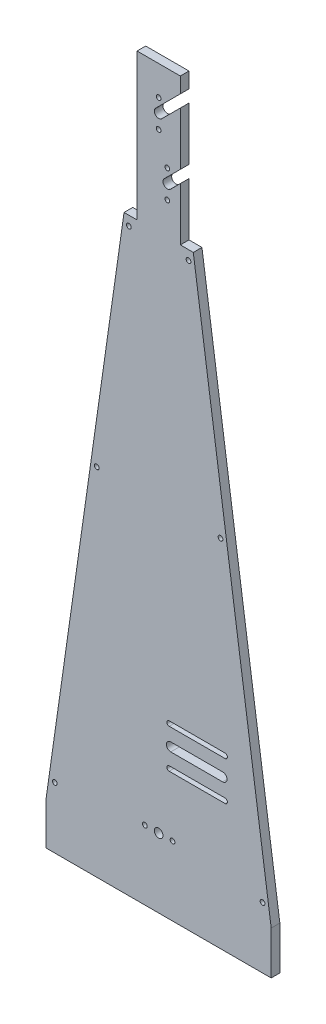
SolidWorks part; units mm, degrees
ref_plane "Ebene vorne" through (0, 0, 0) normal (0, 0, 1) x (1, 0, 0)
ref_plane "Ebene oben" through (0, 0, 0) normal (0, 1, 0) x (1, 0, 0)
ref_plane "Ebene rechts" through (0, 0, 0) normal (1, 0, 0) x (0, 0, -1)
sketch "Skizze1" plane through (0, 0, 0) normal (0, 0, 1) x (1, 0, 0)
  line L0 (-40, 681) -> (-130, 50)
  line L1 (-263.5092, 681) -> (296.6943, 681) construction
  line L2 (0, 800) -> (0, 0)
  line L3 (-25, 800) -> (-25, 681)
  line L4 (-40, 681) -> (-25, 681)
  line L5 (0, 800) -> (0, 850)
  line L7 (-130, 0) -> (-130, 50)
  line L10 (40, 681) -> (25, 681)
  line L12 (-130, 0) -> (0, 0)
  line L13 (-32.9292, 681) -> (-123.0701, 49.0116) construction
  line L14 (-33.0701, 680.0116) -> (-123.0701, 49.0116) construction
  line L15 (-25, 800) -> (-25, 850)
  line L16 (-25, 850) -> (0, 850)
  point P2 (0, 800)
  point P4 (0, 681)
  point P8 (-40, 681)
  point P12 (-119.9898, 70.6083)
  point P18 (-71.4708, 410.7801)
  point P21 (-34.4874, 670.075)
  point P23 (0, 816)
  point P24 (0, 784)
  dimension "D2" = 25
  dimension "D5" = 50
  dimension "D6" = 130
  dimension "D1" = 800
  dimension "D3" = 119
  dimension "D4" = 40
  dimension "D8" = 50
  dimension "D9" = 16
  dimension "D10" = 16
  dimension "D7" = 7
extrude "Aufsatz-Linear austragen1" add sketch "Skizze1" along normal blind 10 contours L2 L12 L7 L0 L4 L3 L15 L16 L5
mirror "Spiegeln1" about plane through (0, 800, 10) normal (1, 0, 0) of "Aufsatz-Linear austragen1"
sketch "Skizze17" plane through (0, 0, 10) normal (0, 0, 1) x (1, 0, 0)
  line L0 (0, 800) -> (28.5355, 828.5355) construction
  line L1 (-3.5355, 803.5355) -> (25, 832.0711)
  line L2 (3.5355, 796.4645) -> (32.0711, 825)
  line L3 (-25, 850) -> (25, 850) construction
  line L4 (25, 850) -> (25, 681) construction
  line L5 (10, 734.4448) -> (28.5355, 752.9803) construction
  line L6 (6.4645, 737.9803) -> (25, 756.5159)
  line L7 (13.5355, 730.9093) -> (32.0711, 749.4448)
  line L8 (-25, 850) -> (0, 850) construction
  line L9 (10, 850) -> (10, 681) construction
  line L10 (-263.5092, 681) -> (296.6943, 681) construction
  arc A0 (-3.5355, 803.5355) -> (3.5355, 796.4645) centre (0, 800) ccw
  arc A1 (32.0711, 825) -> (25, 832.0711) centre (28.5355, 828.5355) ccw
  circle A2 centre (0, 816) radius 2.75
  circle A3 centre (0, 784) radius 2.75
  arc A4 (6.4645, 737.9803) -> (13.5355, 730.9093) centre (10, 734.4448) ccw
  arc A5 (32.0711, 749.4448) -> (25, 756.5159) centre (28.5355, 752.9803) ccw
  circle A6 centre (10, 750.4448) radius 2.75
  circle A7 centre (10, 718.4448) radius 2.75
  point P2 (14.2678, 814.2678)
  point P20 (19.2678, 743.7126)
  point P35 (10, 734.4448)
  dimension "D2" = 5
  dimension "D3" = 5.5
  dimension "D4" = 5.5
  dimension "D6" = 5
  dimension "D10" = 5.5
  dimension "D11" = 5.5
  dimension "D1" = 45
  dimension "D5" = 45
  dimension "D7" = 15
  dimension "D8" = 16
  dimension "D9" = 16
extrude "Schnitt-Linear austragen1" cut sketch "Skizze17" against normal blind 10
hole_wizard "Ø10.0 (10) Durchmesser Bohrung1" positions "Skizze6" profile "Skizze5" hole size "Ø10.0" standard "ISO" end condition through all
sketch "Skizze6" plane through (0, 0, 10) normal (0, 0, 1) x (1, 0, 0)
  line L0 (0, 800) -> (0, 0) construction
  line L1 (-130, 0) -> (130, 0) construction
  point P3 (0, 80)
  point P18 (0, 0)
  dimension "D1" = 80
sketch "Skizze5" plane through (0, 80, 10) normal (1, 0, 0) x (0, -1, 0)
  line L0 (0, 0) -> (0, 10)
  line L1 (0, 10) -> (5, 10)
  line L2 (5, 10) -> (5, 0)
  line L5 (5, 0) -> (0, 0)
  line L11 (0, -6.35) -> (0, 107.95) construction
  dimension "Bohrerdurchmesser" = 10
  dimension "Bohrungstiefe" = 10
hole_wizard "Ø5.5 (5.5) Durchmesser Bohrung2" positions "Skizze7" profile "Skizze8" hole size "Ø5.5" standard "ISO" end condition through all
sketch "Skizze7" plane through (0, 0, 10) normal (0, 0, 1) x (1, 0, 0)
  line L1 (0, 80) -> (-104.9668, 80) construction
  line L3 (0, 80) -> (96.42, 80) construction
  circle A0 centre (0, 80) radius 5 construction
  point P0 (-16, 80)
  point P4 (16, 80)
  dimension "D1" = 16
  dimension "D2" = 16
sketch "Skizze8" plane through (-16, 80, 10) normal (1, 0, 0) x (0, -1, 0)
  line L0 (0, 0) -> (0, 10)
  line L1 (0, 10) -> (2.75, 10)
  line L2 (2.75, 10) -> (2.75, 0)
  line L5 (2.75, 0) -> (0, 0)
  line L11 (0, -6.35) -> (0, 107.95) construction
  dimension "Bohrerdurchmesser" = 5.5
  dimension "Bohrungstiefe" = 10
hole_wizard "Ø10.0 (10) Durchmesser Langloch1" positions "Skizze9" profile "Skizze10" size "Ø10.0" standard "ISO" slot yes end condition through all
sketch "Skizze9" plane through (0, 0, 10) normal (0, 0, 1) x (1, 0, 0)
  line L0 (8.9197, 173.191) -> (78.9197, 173.191) construction
  point P0 (43.9197, 173.191)
  dimension "D1" = 70
sketch "Skizze10" plane through (43.9197, 173.191, 10) normal (1, 0, 0) x (0, -1, 0)
  line L0 (0, 0) -> (0, 10)
  line L1 (0, 10) -> (5, 10)
  line L2 (5, 10) -> (5, 0)
  line L5 (5, 0) -> (0, 0)
  line L11 (0, -6.35) -> (0, 107.95) construction
  dimension "Bohrerdurchmesser" = 10
  dimension "Bohrungstiefe" = 10
hole_wizard "Ø5.5 (5.5) Durchmesser Langloch1" positions "Skizze13" profile "Skizze14" size "Ø5.5" standard "ISO" slot yes end condition through all
sketch "Skizze13" plane through (0, 0, 10) normal (0, 0, 1) x (1, 0, 0)
  line L0 (9.3832, 195.691) -> (79.3832, 195.691) construction
  line L1 (44.3832, 195.691) -> (44.3832, 150.691) construction
  arc A0 (13.9197, 178.191) -> (13.9197, 168.191) centre (13.9197, 173.191) ccw construction
  point P0 (44.3832, 195.691)
  point P4 (44.3832, 150.691)
  point P10 (8.9197, 173.191)
  dimension "D1" = 70
  dimension "D2" = 22.5
  dimension "D3" = 22.5
sketch "Skizze14" plane through (44.3832, 195.691, 10) normal (1, 0, 0) x (0, -1, 0)
  line L0 (0, 0) -> (0, 10)
  line L1 (0, 10) -> (2.75, 10)
  line L2 (2.75, 10) -> (2.75, 0)
  line L5 (2.75, 0) -> (0, 0)
  line L11 (0, -6.35) -> (0, 107.95) construction
  dimension "Bohrerdurchmesser" = 5.5
  dimension "Bohrungstiefe" = 10
hole_wizard "Ø5.5 (5.5) Durchmesser Bohrung3" positions "Skizze19" profile "Skizze18" hole size "Ø5.5" standard "ISO" end condition through all
sketch "Skizze19" plane through (0, 0, 10) normal (0, 0, 1) x (1, 0, 0)
  point P0 (-34.4874, 670.075)
  point P3 (-71.4708, 410.7801)
  point P6 (-119.9898, 70.6083)
sketch "Skizze18" plane through (-34.4874, 670.075, 10) normal (1, 0, 0) x (0, -1, 0)
  line L0 (0, 0) -> (0, 10)
  line L1 (0, 10) -> (2.75, 10)
  line L2 (2.75, 10) -> (2.75, 0)
  line L5 (2.75, 0) -> (0, 0)
  line L11 (0, -6.35) -> (0, 107.95) construction
  dimension "Bohrerdurchmesser" = 5.5
  dimension "Bohrungstiefe" = 10
mirror "Spiegeln2" about plane through (0, 0, 0) normal (1, 0, 0) of "Ø5.5 (5.5) Durchmesser Bohrung3"
